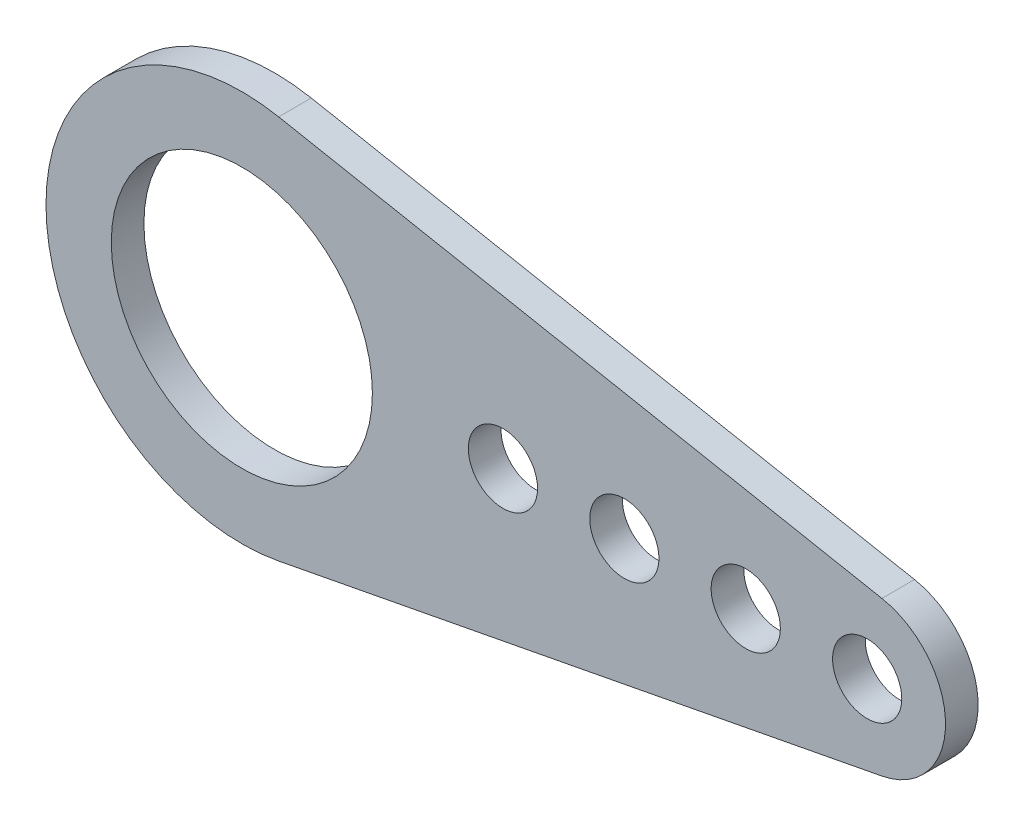
SolidWorks part; units mm, degrees
material "Custom Plastic"
ref_plane "X-Y Datum" through (0, 0, 0) normal (0, 0, 1) x (1, 0, 0)
ref_plane "X-Z Datum" through (0, 0, 0) normal (0, 1, 0) x (1, 0, 0)
ref_plane "Y-Z Datum" through (0, 0, 0) normal (1, 0, 0) x (0, 0, -1)
sketch "Flat sketch" plane through (0, 0, 0) normal (0, 0, 1) x (1, 0, 0)
  line L0 (-12.7, 0) -> (60.833, 0) construction
  line L2 (3.5793, 18.7107) -> (62.2647, 7.4843)
  line L3 (3.5793, -18.7107) -> (62.2647, -7.4843)
  line L4 (62.2647, 7.4843) -> (62.2647, -7.4843) construction
  circle A0 centre (0, 0) radius 12.7
  circle A1 centre (0, 0) radius 19.05
  circle A2 centre (60.833, 0) radius 3.3655
  circle A8 centre (60.833, 0) radius 7.62
  circle A9 centre (49.022, 0) radius 3.3655
  circle A10 centre (37.211, 0) radius 3.3655
  circle A11 centre (25.4, 0) radius 3.3655
  point P5 (12.7, 0)
  point P9 (19.05, 0)
  dimension "D1" = 25.4
  dimension "D2" = 38.1
  dimension "D3" = 6.731
  dimension "D7" = 15.24
  dimension "D5" = 6.35
  dimension "D6" = 11.811
  dimension "D4" = 4
extrude "Extrude face" add sketch "Flat sketch" along normal blind 3.175 contours A1 A0 | A8 A2 | A11 | A10 | A9 | A2 | A8 L2 A1 L3 A11 A10 A9 region at (33.1073, 0, 0) region at (14.2662, 11.7958, 0) region at (66.5395, 4.7183, 0) region at (60.833, 0, 0) region at (49.022, 0, 0) region at (37.211, 0, 0) region at (25.4, 0, 0)
extrude "Extrude cut - holes" cut sketch "Flat sketch<4>" along normal up to surface (3.175 mm away) contours A11 | A10 | A9 | A2 region at (60.833, 0, 0) region at (49.022, 0, 0) region at (37.211, 0, 0) region at (25.4, 0, 0) up to face at (12.7, 0, 3.175)
sketch "Flat sketch<4>" plane through (0, 0, 0) normal (0, 0, 1) x (1, 0, 0) same geometry as "Flat sketch"
equation "\"Torsion Bar O.D.\"= 1in"
equation "\"Lever I.D. Torsion O.D. Clearance\"= 0"
equation "\"Lever I.D.\"= \"Torsion Bar O.D.\" + \"Lever I.D. Torsion O.D. Clearance\""
equation "\"D1@Flat sketch\" = \"Lever I.D.\""
equation "\"Lever O.D.\"= 1.5"
equation "\"D2@Flat sketch\" = \"Lever O.D.\""
equation "\"Lever Rod end I.D.\"= 0.265"
equation "\"D3@Flat sketch\" = \"Lever Rod end I.D.\""
equation "\"Distance b/w Lever Rod end holes\"= 0"
equation "\"Number of Lever Rod end holes\"= 0"
equation "\"Lever arc radius\"= 0.5"
equation "\"Lever rod end hole and Lever O.D. clearance\"= 0.25"
equation "\"Lever thickness\"= 1 / 8in"
equation "\"D1@Extrude face\" = \"Lever thickness\""
equation "\"D5@Flat sketch\"=\"Lever rod end hole and Lever O.D. clearance\""
